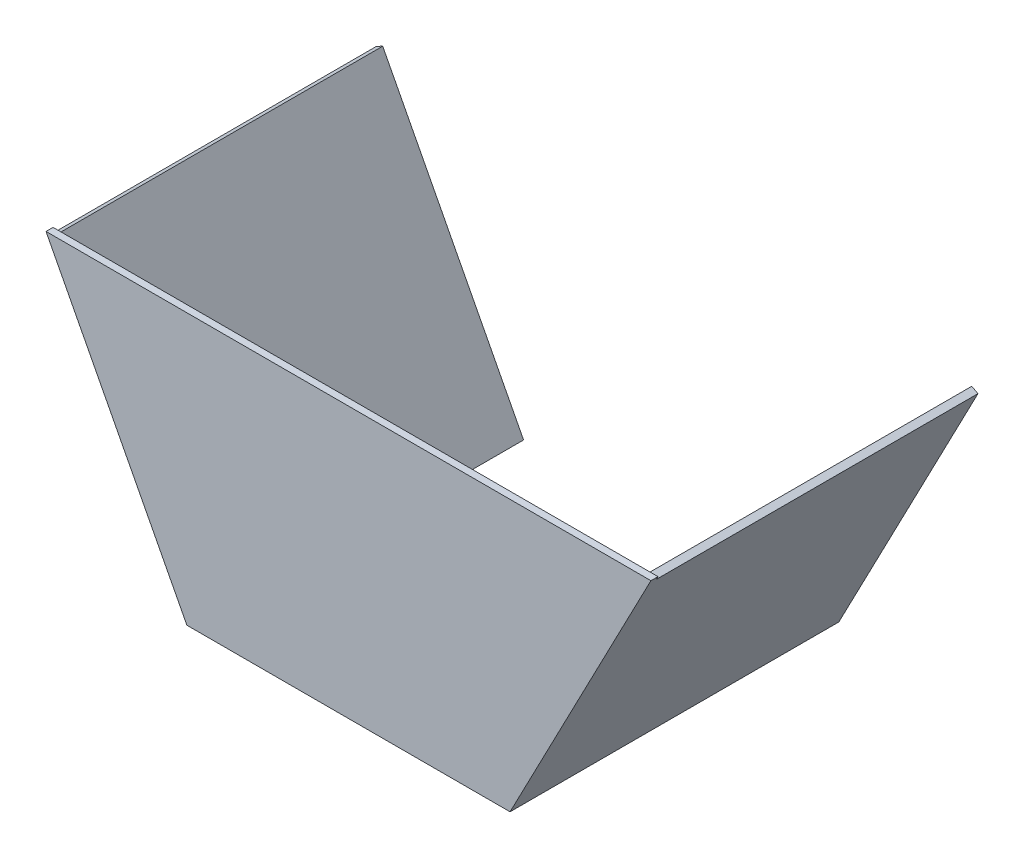
SolidWorks part; units mm, degrees
ref_plane "Front Plane" through (0, 0, 0) normal (0, 0, 1) x (1, 0, 0)
ref_plane "Top Plane" through (0, 0, 0) normal (0, 1, 0) x (1, 0, 0)
ref_plane "Right Plane" through (0, 0, 0) normal (1, 0, 0) x (0, 0, -1)
sketch "Sketch1" plane through (0, 0, 0) normal (0, 0, 1) x (1, 0, 0)
  line L0 (-138.5, 0) -> (138.5, 0) construction
  line L1 (-138.5, 0) -> (-265.4809, 243.928)
  line L2 (138.5, 0) -> (265.4809, 243.928)
  line L3 (-138.5, 0) -> (-145.6589, 0)
  line L4 (-145.6589, 0) -> (-271.1134, 240.9959)
  line L5 (-271.1134, 240.9959) -> (-265.4809, 243.928)
  line L6 (138.5, 0) -> (145.6589, 0)
  line L7 (145.6589, 0) -> (271.1134, 240.9959)
  line L8 (271.1134, 240.9959) -> (265.4809, 243.928)
  point P4 (0, 0)
  dimension "D1" = 62.5
  dimension "D2" = 62.5
  dimension "D3" = 277
  dimension "D4" = 275
  dimension "D5" = 275
  dimension "D6" = 6.35
  dimension "D7" = 6.35
extrude "Boss-Extrude1" add sketch "Sketch1" along normal blind 290
sketch "Sketch2" plane through (0, 0, 290) normal (0, 0, 1) x (1, 0, 0)
  line L0 (-145.6589, 0) -> (-272.6397, 243.928)
  line L1 (-272.6397, 243.928) -> (272.6397, 243.928)
  line L2 (272.6397, 243.928) -> (145.6589, 0)
  line L3 (145.6589, 0) -> (-145.6589, 0)
  line L4 (-271.1134, 240.9959) -> (-145.6589, 0) construction
  line L5 (145.6589, 0) -> (271.1134, 240.9959) construction
extrude "Boss-Extrude2" add sketch "Sketch2" along normal blind 6.35
sketch "Sketch3" plane through (0, 0, 0) normal (1, 0, 0) x (0, 0, -1)
  line L0 (55, 0) -> (-55, 0) construction
  line L1 (-290, 243.928) -> (-290, 0) construction
  circle A0 centre (-152.5, 137.5) radius 137.5 construction
  dimension "D1" = 275
